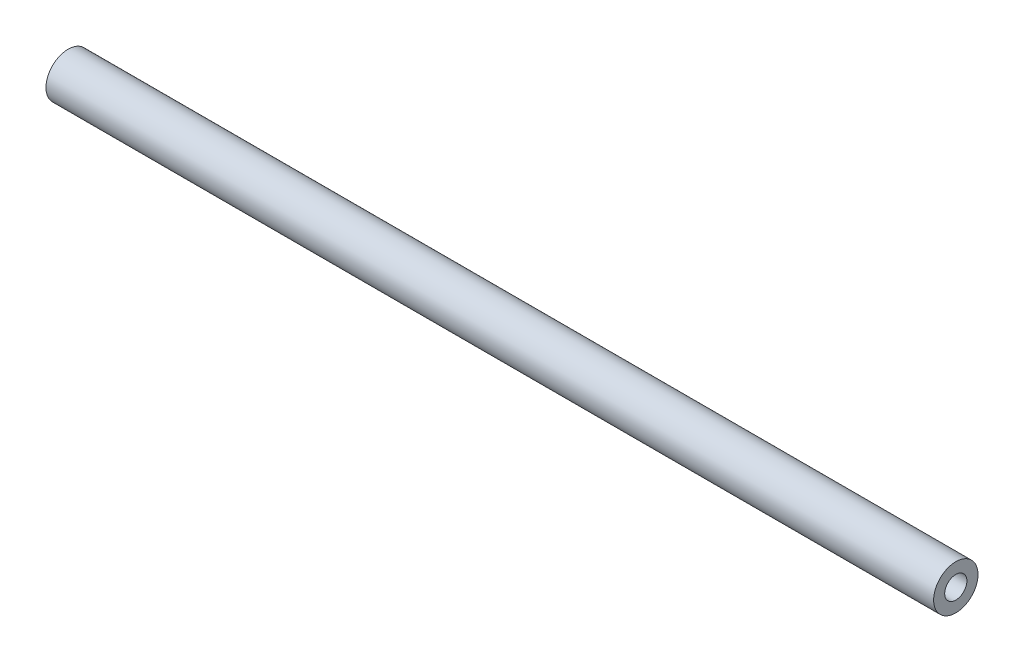
SolidWorks part; units mm, degrees
ref_plane "Front Plane" through (0, 0, 0) normal (0, 0, 1) x (1, 0, 0)
ref_plane "Top Plane" through (0, 0, 0) normal (0, 1, 0) x (1, 0, 0)
ref_plane "Right Plane" through (0, 0, 0) normal (1, 0, 0) x (0, 0, -1)
sketch "Sketch1" plane through (0, 0, 0) normal (1, 0, 0) x (0, 0, -1)
  circle A0 centre (0, 0) radius 6.35
  circle A1 centre (0, 0) radius 12.7
  dimension "D1" = 12.7
  dimension "D2" = 25.4
extrude "Boss-Extrude1" add sketch "Sketch1" along normal blind 508
